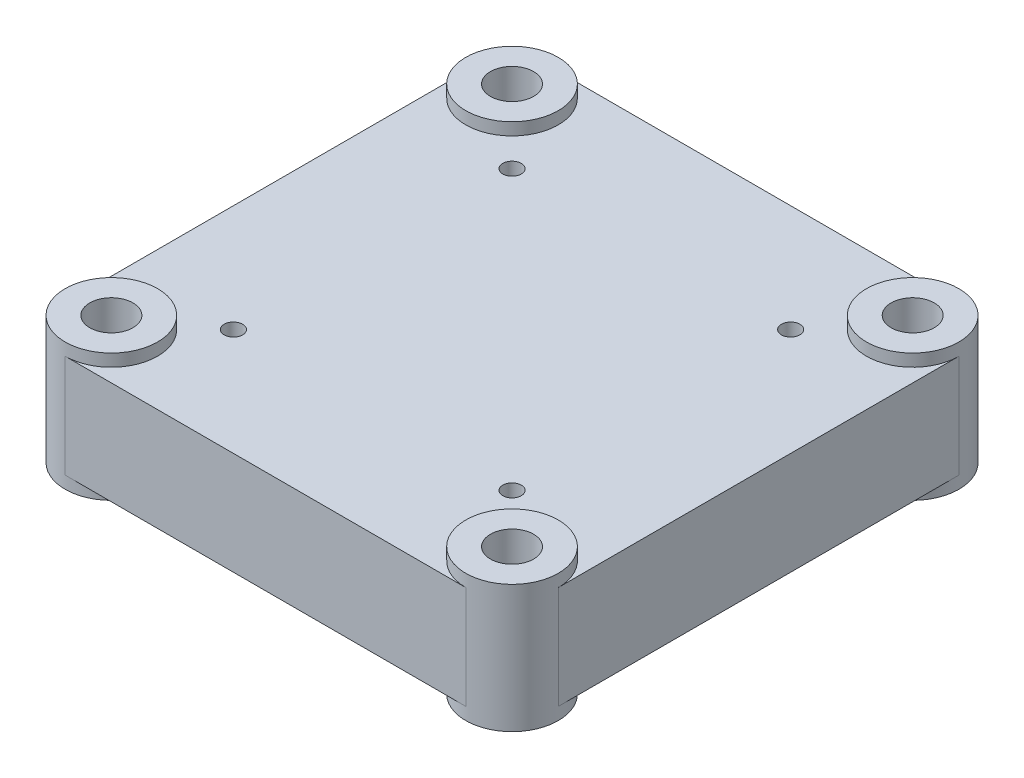
SolidWorks part; units mm, degrees
ref_plane "Front Plane" through (0, 0, 0) normal (0, 0, 1) x (1, 0, 0)
ref_plane "Top Plane" through (0, 0, 0) normal (0, 1, 0) x (1, 0, 0)
ref_plane "Right Plane" through (0, 0, 0) normal (1, 0, 0) x (0, 0, -1)
sketch "Sketch1" plane through (0, 0, 0) normal (0, 1, 0) x (1, 0, 0)
  line L0 (51.9659, 0) -> (-55.8196, 0) construction
  line L1 (-32.5, -40) -> (32.5, -40)
  line L2 (-40, -32.5) -> (-40, 32.5)
  line L3 (-32.5, 40) -> (32.5, 40)
  line L4 (40, -32.5) -> (40, 32.5)
  line L5 (-40, -40) -> (40, 40) construction
  line L6 (-40, 40) -> (40, -40) construction
  line L7 (0, -48.933) -> (0, 55.862) construction
  circle A0 centre (32.5, 32.5) radius 3.5
  circle A1 centre (-32.5, -32.5) radius 3.5
  circle A2 centre (-32.5, 32.5) radius 3.5
  circle A3 centre (32.5, -32.5) radius 3.5
  arc A5 (-32.5, -40) -> (-40, -32.5) centre (-32.5, -32.5) cw
  arc A6 (32.5, -40) -> (40, -32.5) centre (32.5, -32.5) ccw
  arc A7 (32.5, 40) -> (40, 32.5) centre (32.5, 32.5) cw
  arc A8 (-40, 32.5) -> (-32.5, 40) centre (-32.5, 32.5) cw
  circle A9 centre (22.6005, -22.6005) radius 1.5
  circle A10 centre (-22.6005, -22.6005) radius 1.5
  circle A11 centre (-22.6005, 22.6005) radius 1.5
  circle A12 centre (22.6005, 22.6005) radius 1.5
  point P0 (0, 0)
  dimension "D3" = 7
  dimension "D5" = 7.5
  dimension "D6" = 3
  dimension "D7" = 14
  dimension "D1" = 80
  dimension "D2" = 80
  dimension "D4" = 7.5
extrude "Boss-Extrude1" add sketch "Sketch1" along normal blind 16.7
sketch "Sketch4" plane through (0, 16.7, 0) normal (0, 1, 0) x (1, 0, 0)
  line L0 (37.9809, 0) -> (-39.1715, 0) construction
  line L1 (0, 43.4251) -> (0, -51.6078) construction
  circle A0 centre (32.5, 32.5) radius 7.5
  circle A1 centre (32.5, -32.5) radius 7.5
  circle A4 centre (32.5, 32.5) radius 3.5
  circle A5 centre (32.5, -32.5) radius 3.5
  circle A8 centre (-32.5, -32.5) radius 3.5
  circle A9 centre (-32.5, -32.5) radius 7.5
  circle A10 centre (-32.5, 32.5) radius 3.5
  circle A11 centre (-32.5, 32.5) radius 7.5
extrude "Boss-Extrude5" add sketch "Sketch4" along normal blind 2 from surface starting at face at (0, 16.7, 0)
sketch "Sketch5" plane through (0, 0, 0) normal (0, -1, 0) x (1, 0, 0)
  circle A0 centre (0, 0) radius 17.4
extrude "Boss-Extrude7" add sketch "Sketch5" along normal blind 8 contours A0
extrude "Boss-Extrude8" add sketch "Sketch4<2>" against normal blind 2 from surface starting at face at (0, 0, -17.4)
sketch "Sketch4<2>" plane through (0, 16.7, 0) normal (0, 1, 0) x (1, 0, 0) same geometry as "Sketch4"
